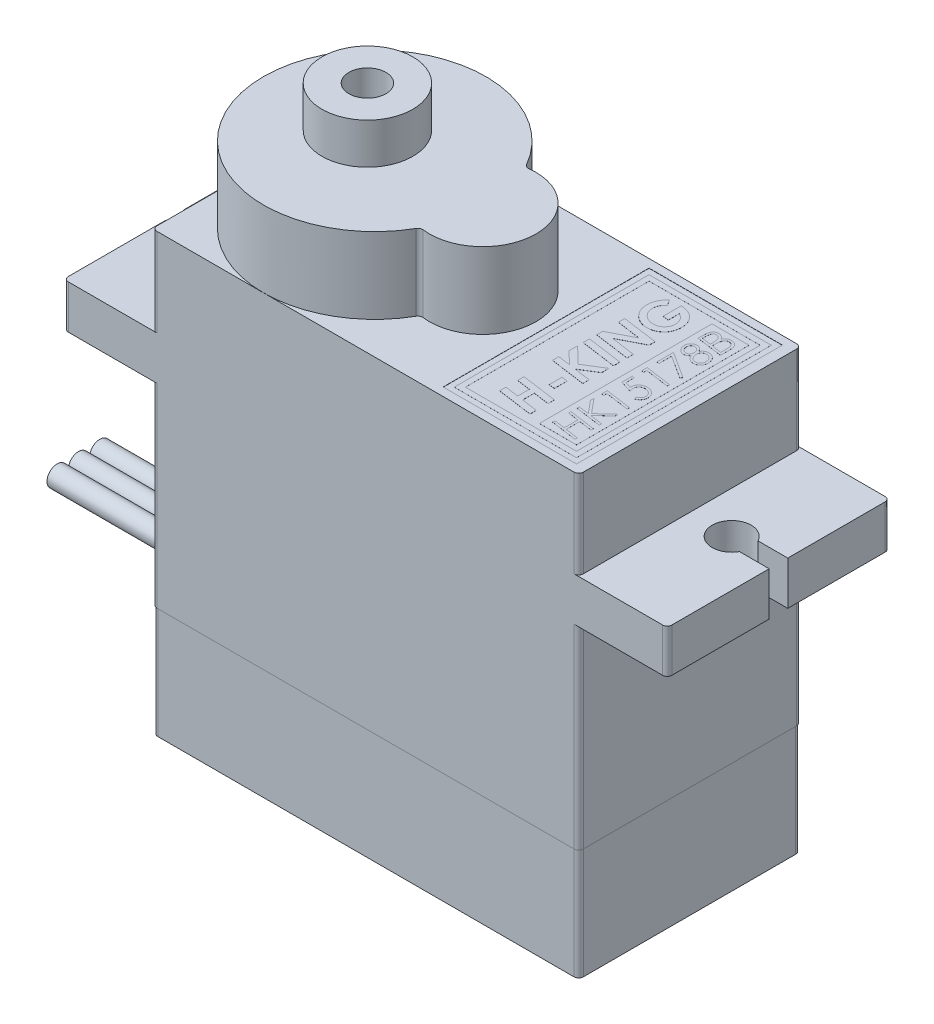
SolidWorks part; units mm, degrees
note: The reader was unsure of these and kept them because the rebuilt part matched: shared geometry of "Schizzo1<2>".
material "ABS generico"
ref_plane "Piano frontale" through (0, 0, 0) normal (0, 0, 1) x (1, 0, 0)
ref_plane "Piano superiore" through (0, 0, 0) normal (0, 1, 0) x (1, 0, 0)
ref_plane "Piano destro" through (0, 0, 0) normal (1, 0, 0) x (0, 0, -1)
sketch "Schizzo1" plane through (0, 0, 0) normal (0, 1, 0) x (1, 0, 0)
  line L1 (-11.5, -6) -> (11.5, -6)
  line L2 (-11.5, -6) -> (-11.5, 6)
  line L3 (-11.5, 6) -> (11.5, 6)
  line L4 (11.5, -6) -> (11.5, 6)
  line L5 (-11.5, -6) -> (11.5, 6) construction
  line L6 (-11.5, 6) -> (11.5, -6) construction
  point P0 (0, 0)
  dimension "D1" = 23
  dimension "D2" = 12
extrude "Estrusione-Estrusione1" add sketch "Schizzo1" along normal blind 10.5
sketch "Schizzo2" plane through (0, 0, 0) normal (0, -1, 0) x (1, 0, 0)
  line L18 (11.475, -5.975) -> (11.475, 5.975)
  line L19 (-11.475, -5.975) -> (11.475, -5.975)
  line L20 (-11.475, 5.975) -> (-11.475, -5.975)
  line L21 (11.475, 5.975) -> (-11.475, 5.975)
  line L22 (11.475, -5.975) -> (11.475, 5.975)
  line L23 (-11.475, -5.975) -> (11.475, -5.975)
  line L24 (-11.475, 5.975) -> (-11.475, -5.975)
  line L25 (11.475, 5.975) -> (-11.475, 5.975)
  dimension "D1" = 0.025
extrude "Estrusione-Estrusione2" add sketch "Schizzo2" along normal blind 6
sketch "Schizzo3" plane through (-11.475, 0, 0) normal (-1, 0, 0) x (0, 0, 1)
  line L0 (-6, 0) -> (6, 0) construction
  line L1 (-2.35, -2.7) -> (2.35, -2.7)
  line L2 (-2.35, -2.7) -> (-2.35, 0)
  line L3 (-2.35, 0) -> (2.35, 0)
  line L4 (2.35, -2.7) -> (2.35, 0)
  line L5 (-2.35, -2.7) -> (2.35, 0) construction
  line L6 (-2.35, 0) -> (2.35, -2.7) construction
  line L7 (-1.8, -2.15) -> (1.8, -2.15)
  line L8 (1.8, -2.15) -> (1.8, -0.55)
  line L9 (-1.8, -0.55) -> (1.8, -0.55)
  line L10 (-1.8, -2.15) -> (-1.8, -0.55)
  point P0 (0, -1.35)
  dimension "D1" = 4.7
  dimension "D2" = 2.7
  dimension "D3" = 0.55
extrude "Estrusione-Estrusione3" add sketch "Schizzo3" along normal blind 1.3
sketch "Schizzo4" plane through (-11.475, 0, 0) normal (-1, 0, 0) x (0, 0, 1)
  line L0 (-1.15, -1.35) -> (0, -1.35) construction
  line L1 (0, -1.35) -> (1.15, -1.35) construction
  line L2 (-1.8, -1.35) -> (-1.15, -1.35) construction
  line L3 (-1.8, -0.55) -> (-1.8, -2.15) construction
  line L4 (1.15, -1.35) -> (1.8, -1.35) construction
  line L5 (1.8, -2.15) -> (1.8, -0.55) construction
  circle A0 centre (-1.15, -1.35) radius 0.55
  circle A1 centre (0, -1.35) radius 0.55
  circle A2 centre (1.15, -1.35) radius 0.55
  dimension "D1" = 1.1
  dimension "D2" = 1.15
extrude "Estrusione-Estrusione4" add sketch "Schizzo4" along normal blind 10
sketch "Schizzo5" plane through (0, 10.5, 0) normal (0, 1, 0) x (1, 0, 0)
  line L0 (11.5, 6) -> (-11.5, 6) construction
  line L1 (-16.275, -6) -> (16.275, -6)
  line L2 (-16.275, -6) -> (-16.275, 6)
  line L3 (-16.275, 6) -> (16.275, 6)
  line L4 (16.275, -6) -> (16.275, 6)
  line L5 (-16.275, -6) -> (16.275, 6) construction
  line L6 (-16.275, 6) -> (16.275, -6) construction
  line L7 (-13.75, 0) -> (0, 0) construction
  line L8 (0, 0) -> (13.75, 0) construction
  circle A0 centre (-13.75, 0) radius 1.05
  circle A1 centre (13.75, 0) radius 1.05
  point P0 (0, 0)
  dimension "D2" = 2.1
  dimension "D1" = 32.55
  dimension "D3" = 13.75
extrude "Estrusione-Estrusione5" add sketch "Schizzo5" along normal blind 2.35
sketch "Schizzo6" plane through (0, 12.85, 0) normal (0, 1, 0) x (1, 0, 0)
  line L0 (16.275, -6) -> (16.275, 6) construction
  line L1 (16.275, 0.5) -> (13.275, 0.5)
  line L2 (16.275, 0.5) -> (16.275, -0.5)
  line L3 (16.275, -0.5) -> (13.275, -0.5)
  line L4 (13.275, 0.5) -> (13.275, -0.5)
  line L5 (-16.275, 6) -> (-16.275, -6) construction
  line L6 (-16.275, 0.5) -> (-13.275, 0.5)
  line L7 (-16.275, 0.5) -> (-16.275, -0.5)
  line L8 (-16.275, -0.5) -> (-13.275, -0.5)
  line L9 (-13.275, 0.5) -> (-13.275, -0.5)
  line L10 (13.275, 0) -> (0, 0) construction
  line L11 (0, 0) -> (-13.275, 0) construction
  dimension "D1" = 1
  dimension "D2" = 3
extrude "Taglio-Estrusione1" cut sketch "Schizzo6" against normal blind 3
extrude "Estrusione-Estrusione6" add sketch "Schizzo1<2>" along normal blind 4.75 from vertex at 12.85 starting at point (-16.275, 12.85, 6)
sketch "Schizzo1<2>" plane through (0, 0, 0) normal (0, 1, 0) x (1, 0, 0) same geometry as "Schizzo1"
sketch "Schizzo7" plane through (0, 17.6, 0) normal (0, 1, 0) x (1, 0, 0)
  line L0 (-11.5, -6) -> (11.5, -6) construction
  line L1 (-11.5, 6) -> (-11.5, -6) construction
  line L2 (3.2, 0) -> (3.2, 6) construction
  line L3 (11.5, 6) -> (-11.5, 6) construction
  arc A0 (-0.2069, 2.8254) -> (-0.2069, -2.8254) centre (-5.5, 0) ccw
  arc A1 (-0.2069, -2.8254) -> (-0.2069, 2.8254) centre (0.325, 0) ccw
  dimension "D1" = 5.75
  dimension "D2" = 14.7
extrude "Estrusione-Estrusione7" add sketch "Schizzo7" along normal blind 4.1
fillet "Raccordo2" radius 0.25 10 edges at (-0.2069, 19.65, 2.8254) (-0.2069, 19.65, -2.8254) (16.275, 11.675, -6) (16.275, 11.675, 6) (-16.275, 11.675, -6) (-16.275, 11.675, 6)
sketch "Schizzo8" plane through (0, 0, 0) normal (0, 0, 1) x (1, 0, 0)
  line L0 (-5.8949, 21.7) -> (-5.8949, 24.2)
  line L1 (-0.2898, 21.7) -> (-11.5, 21.7) construction
  line L2 (-5.8949, 24.2) -> (-8.3449, 24.2)
  line L3 (-8.3449, 24.2) -> (-8.3449, 22)
  line L4 (-8.3449, 22) -> (-7.5596, 22)
  line L5 (-7.5596, 22) -> (-7.5596, 21.7)
  line L6 (-7.5596, 21.7) -> (-5.8949, 21.7)
  dimension "D1" = 2.45
  dimension "D2" = 2.5
  dimension "D3" = 0.3
revolve "Rivoluzione1" add sketch "Schizzo8" angle 360 about L0
fillet "Raccordo4" radius 0.25 8 edges at (11.475, -3, 5.975) (11.475, -3, -5.975) (-11.475, -3, 5.975) (-11.475, -3, -5.975) (-12.125, -2.7, -2.35) (-12.1375, 0, -2.35) (-12.125, -2.7, 2.35) (-12.1375, 0, 2.35)
sketch "Schizzo9" plane through (0, 24.2, 0) normal (0, 1, 0) x (1, 0, 0)
  circle A0 centre (-5.8949, 0) radius 1
  dimension "D1" = 2
extrude "Taglio-Estrusione2" cut sketch "Schizzo9" against normal blind 3
cosmetic thread "Filettatura cosmetica1" parameters "D2"=6
sketch "Schizzo10" plane through (0, 17.6, 0) normal (0, 1, 0) x (1, 0, 0)
  line L1 (3.7428, -5.5524) -> (10.9353, -5.5524)
  line L2 (3.7428, -5.5524) -> (3.7428, 5.5524)
  line L3 (3.7428, 5.5524) -> (10.9353, 5.5524)
  line L4 (10.9353, -5.5524) -> (10.9353, 5.5524)
  line L5 (3.7428, -5.5524) -> (10.9353, 5.5524) construction
  line L6 (3.7428, 5.5524) -> (10.9353, -5.5524) construction
  point P0 (7.3391, 0)
extrude "Taglio-Estrusione3" cut sketch "Schizzo10" against normal blind 0.01
sketch "Schizzo11" plane through (0, 17.59, 0) normal (0, 1, 0) x (1, 0, 0)
  line L0 (3.7428, 0) -> (10.9353, 0) construction
  line L1 (3.7428, 5.5524) -> (3.7428, -5.5524) construction
  line L2 (10.9353, -5.5524) -> (10.9353, 5.5524) construction
  line L13 (10.3353, 4.9524) -> (4.3428, 4.9524)
  line L14 (4.3428, 4.9524) -> (4.3428, -4.9524)
  line L15 (4.3428, -4.9524) -> (10.3353, -4.9524)
  line L16 (10.3353, -4.9524) -> (10.3353, 4.9524)
  line L17 (4.0428, -5.2524) -> (10.6353, -5.2524)
  line L18 (10.6353, -5.2524) -> (10.6353, 5.2524)
  line L19 (4.0428, 5.2524) -> (4.0428, -5.2524)
  line L20 (10.6353, 5.2524) -> (4.0428, 5.2524)
  line L21 (4.0428, -5.2524) -> (10.6353, -5.2524)
  line L22 (10.6353, -5.2524) -> (10.6353, 5.2524)
  line L23 (4.0428, 5.2524) -> (4.0428, -5.2524)
  line L24 (10.6353, 5.2524) -> (4.0428, 5.2524)
  line L25 (9.0353, 4.6524) -> (9.0353, 4.9524) construction
  line L26 (8.0353, -4.6524) -> (10.0353, -4.6524)
  line L27 (8.0353, -4.6524) -> (8.0353, 4.6524)
  line L28 (8.0353, 4.6524) -> (10.0353, 4.6524)
  line L29 (10.0353, -4.6524) -> (10.0353, 4.6524)
  line L30 (8.0353, -4.6524) -> (10.0353, 4.6524) construction
  line L31 (8.0353, 4.6524) -> (10.0353, -4.6524) construction
  line L32 (10.0353, 0) -> (10.3353, 0) construction
  line L33 (9.7353, 4.6524) -> (9.7353, -4.6524) construction
  line L34 (7.3391, -4.9524) -> (7.3391, 4.9524) construction
  text T0 "<i>HK15178B</i>" font "Century Gothic" height 1.4
  text T1 "<b><i>H-KING</i></b>" font "Century Gothic" height 1.9
  point P14 (9.0353, 0)
  dimension "D1" = 0.3
  dimension "D2" = 0.3
  dimension "D3" = 0.3
  dimension "D4" = 2
  dimension "D5" = 0.3
  dimension "D6" = 0.6
extrude "Estrusione-Estrusione8" add sketch "Schizzo11" along normal blind 0.0025 contours L22 L24 L23 L21 L16 L15 L14 L13 | L26 L29 L28 L27
sketch "Schizzo13" plane through (0, 17.59, 0) normal (0, 1, 0) x (1, 0, 0)
  line L0 (3.7428, 0) -> (10.9353, 0) construction
  line L13 (10.3353, 4.9524) -> (4.3428, 4.9524) construction
  line L14 (4.3428, 4.9524) -> (4.3428, -4.9524) construction
  line L15 (4.3428, -4.9524) -> (10.3353, -4.9524) construction
  line L16 (10.3353, -4.9524) -> (10.3353, 4.9524) construction
  line L21 (4.0428, -5.2524) -> (10.6353, -5.2524) construction
  line L22 (10.6353, -5.2524) -> (10.6353, 5.2524) construction
  line L23 (4.0428, 5.2524) -> (4.0428, -5.2524) construction
  line L24 (10.6353, 5.2524) -> (4.0428, 5.2524) construction
  line L25 (9.0353, 4.6524) -> (9.0353, 4.9524) construction
  line L26 (8.0353, -4.6524) -> (10.0353, -4.6524) construction
  line L27 (8.0353, -4.6524) -> (8.0353, 4.6524) construction
  line L28 (8.0353, 4.6524) -> (10.0353, 4.6524) construction
  line L29 (10.0353, -4.6524) -> (10.0353, 4.6524) construction
  line L30 (8.0353, -4.6524) -> (10.0353, 4.6524) construction
  line L31 (8.0353, 4.6524) -> (10.0353, -4.6524) construction
  line L32 (10.0353, 0) -> (10.3353, 0) construction
  line L33 (9.7353, 4.6524) -> (9.7353, -4.6524) construction
  line L34 (7.3391, -4.9524) -> (7.3391, 4.9524) construction
  text T0 "<i>HK15178B</i>" font "Century Gothic" height 1.4
  text T1 "<b><i>H-KING</i></b>" font "Century Gothic" height 1.9
  point P14 (9.0353, 0)
  dimension "D3" = 0.3
  dimension "D4" = 2
  dimension "D5" = 0.3
  dimension "D6" = 0.3
extrude "Estrusione-Estrusione9" add sketch "Schizzo13" along normal blind 0.005
fillet "Raccordo5" radius 0.25 4 edges
sketch "Sketch1" plane through (0, 0, -6) normal (0, 0, -1) x (-1, 0, 0)
  line L0 (5.8949, 24.2) -> (5.8949, 12.0928)
  line L1 (8.3449, 24.2) -> (3.4449, 24.2) construction
sketch "Sketch2" plane through (0, 12.85, 0) normal (0, 1, 0) x (1, 0, 0)
  circle A0 centre (13.7471, -0.0043) radius 1.0552
